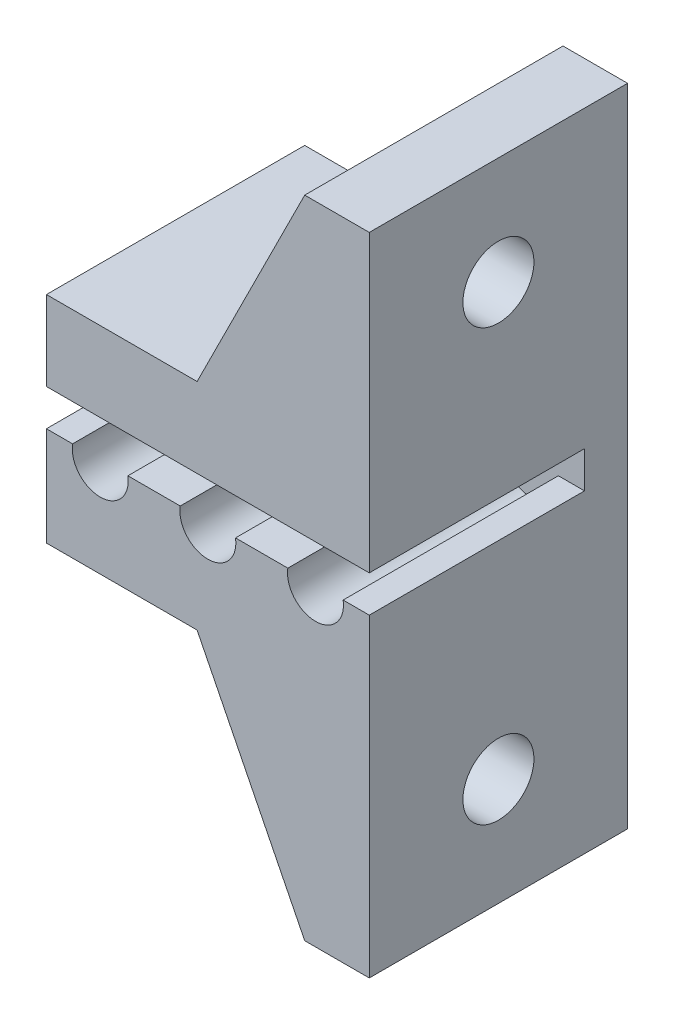
SolidWorks part; units mm, degrees
note: The reader was unsure of these and kept them because the rebuilt part matched: shared geometry of "Sketch2<4>".
ref_plane "Front Plane" through (0, 0, 0) normal (0, 0, 1) x (1, 0, 0)
ref_plane "Top Plane" through (0, 0, 0) normal (0, 1, 0) x (1, 0, 0)
ref_plane "Right Plane" through (0, 0, 0) normal (1, 0, 0) x (0, 0, -1)
sketch "Model" plane through (0, 0, 0) normal (0, 0, 1) x (1, 0, 0)
  line L11 (258.5262, 236.0812) -> (148.5257, 236.0812)
  line L13 (256.5897, 234.1812) -> (255.4627, 234.1812)
  line L14 (251.5897, 234.1812) -> (250.4627, 234.1812)
  line L15 (246.5897, 234.1812) -> (245.4627, 234.1812)
  line L16 (241.5897, 234.1812) -> (240.4626, 234.1812)
  line L17 (236.5896, 234.1812) -> (235.4626, 234.1812)
  line L18 (231.5896, 234.1812) -> (230.4626, 234.1812)
  line L19 (226.5896, 234.1812) -> (225.4626, 234.1812)
  line L20 (221.5896, 234.1812) -> (220.4625, 234.1812)
  line L21 (216.5895, 234.1812) -> (215.4625, 234.1812)
  line L22 (211.5895, 234.1812) -> (210.4625, 234.1812)
  line L23 (206.5895, 234.1812) -> (205.4625, 234.1812)
  line L24 (201.5895, 234.1812) -> (200.4624, 234.1812)
  line L25 (196.5894, 234.1812) -> (195.4624, 234.1812)
  line L26 (191.5894, 234.1812) -> (190.4624, 234.1812)
  line L27 (186.5894, 234.1812) -> (185.4624, 234.1812)
  line L28 (181.5894, 234.1812) -> (180.4623, 234.1812)
  line L29 (176.5893, 234.1812) -> (175.4623, 234.1812)
  line L30 (171.5893, 234.1812) -> (170.4623, 234.1812)
  line L31 (166.5893, 234.1812) -> (165.4623, 234.1812)
  line L32 (161.5892, 234.1812) -> (160.4622, 234.1812)
  line L33 (156.5892, 234.1812) -> (155.4622, 234.1812)
  line L34 (151.5892, 234.1812) -> (150.4622, 234.1812)
  line L58 (148.5257, 234.1812) -> (258.5262, 234.1812) construction
  arc A194 (260.2901, 234.1505) -> (259.9786, 233.8062) centre (260.4627, 233.6812) ccw
  arc A195 (258.9429, 232.7402) -> (259.9786, 233.8062) centre (258.5262, 234.1812) ccw
  arc A196 (258.9429, 232.7402) -> (258.1096, 232.7402) centre (258.5262, 232.0185) ccw
  arc A197 (257.0739, 233.8062) -> (258.1096, 232.7402) centre (258.5262, 234.1812) ccw
  arc A198 (257.0739, 233.8062) -> (256.5897, 234.1812) centre (256.5897, 233.6812) ccw
  arc A199 (255.4627, 234.1812) -> (254.9786, 233.8062) centre (255.4627, 233.6812) ccw
  arc A200 (253.9429, 232.7402) -> (254.9786, 233.8062) centre (253.5262, 234.1812) ccw
  arc A201 (253.9429, 232.7402) -> (253.1095, 232.7402) centre (253.5262, 232.0185) ccw
  arc A202 (252.0738, 233.8062) -> (253.1095, 232.7402) centre (253.5262, 234.1812) ccw
  arc A203 (252.0738, 233.8062) -> (251.5897, 234.1812) centre (251.5897, 233.6812) ccw
  arc A204 (250.4627, 234.1812) -> (249.9786, 233.8062) centre (250.4627, 233.6812) ccw
  arc A205 (248.9429, 232.7402) -> (249.9786, 233.8062) centre (248.5262, 234.1812) ccw
  arc A206 (248.9429, 232.7402) -> (248.1095, 232.7402) centre (248.5262, 232.0185) ccw
  arc A207 (247.0738, 233.8062) -> (248.1095, 232.7402) centre (248.5262, 234.1812) ccw
  arc A208 (247.0738, 233.8062) -> (246.5897, 234.1812) centre (246.5897, 233.6812) ccw
  arc A209 (245.4627, 234.1812) -> (244.9785, 233.8062) centre (245.4627, 233.6812) ccw
  arc A210 (243.9428, 232.7402) -> (244.9785, 233.8062) centre (243.5262, 234.1812) ccw
  arc A211 (243.9428, 232.7402) -> (243.1095, 232.7402) centre (243.5262, 232.0185) ccw
  arc A212 (242.0738, 233.8062) -> (243.1095, 232.7402) centre (243.5262, 234.1812) ccw
  arc A213 (242.0738, 233.8062) -> (241.5897, 234.1812) centre (241.5897, 233.6812) ccw
  arc A214 (240.4626, 234.1812) -> (239.9785, 233.8062) centre (240.4626, 233.6812) ccw
  arc A215 (238.9428, 232.7402) -> (239.9785, 233.8062) centre (238.5261, 234.1812) ccw
  arc A216 (238.9428, 232.7402) -> (238.1095, 232.7402) centre (238.5261, 232.0185) ccw
  arc A217 (237.0738, 233.8062) -> (238.1095, 232.7402) centre (238.5261, 234.1812) ccw
  arc A218 (237.0738, 233.8062) -> (236.5896, 234.1812) centre (236.5896, 233.6812) ccw
  arc A219 (235.4626, 234.1812) -> (234.9785, 233.8062) centre (235.4626, 233.6812) ccw
  arc A220 (233.9428, 232.7402) -> (234.9785, 233.8062) centre (233.5261, 234.1812) ccw
  arc A221 (233.9428, 232.7402) -> (233.1094, 232.7402) centre (233.5261, 232.0185) ccw
  arc A222 (232.0737, 233.8062) -> (233.1094, 232.7402) centre (233.5261, 234.1812) ccw
  arc A223 (232.0737, 233.8062) -> (231.5896, 234.1812) centre (231.5896, 233.6812) ccw
  arc A224 (230.4626, 234.1812) -> (229.9785, 233.8062) centre (230.4626, 233.6812) ccw
  arc A225 (228.9428, 232.7402) -> (229.9785, 233.8062) centre (228.5261, 234.1812) ccw
  arc A226 (228.9428, 232.7402) -> (228.1094, 232.7402) centre (228.5261, 232.0185) ccw
  arc A227 (227.0737, 233.8062) -> (228.1094, 232.7402) centre (228.5261, 234.1812) ccw
  arc A228 (227.0737, 233.8062) -> (226.5896, 234.1812) centre (226.5896, 233.6812) ccw
  arc A229 (225.4626, 234.1812) -> (224.9784, 233.8062) centre (225.4626, 233.6812) ccw
  arc A230 (223.9427, 232.7402) -> (224.9784, 233.8062) centre (223.5261, 234.1812) ccw
  arc A231 (223.9427, 232.7402) -> (223.1094, 232.7402) centre (223.5261, 232.0185) ccw
  arc A232 (222.0737, 233.8062) -> (223.1094, 232.7402) centre (223.5261, 234.1812) ccw
  arc A233 (222.0737, 233.8062) -> (221.5896, 234.1812) centre (221.5896, 233.6812) ccw
  arc A234 (220.4625, 234.1812) -> (219.9784, 233.8062) centre (220.4625, 233.6812) ccw
  arc A235 (218.9427, 232.7402) -> (219.9784, 233.8062) centre (218.526, 234.1812) ccw
  arc A236 (218.9427, 232.7402) -> (218.1094, 232.7402) centre (218.526, 232.0185) ccw
  arc A237 (217.0737, 233.8062) -> (218.1094, 232.7402) centre (218.526, 234.1812) ccw
  arc A238 (217.0737, 233.8062) -> (216.5895, 234.1812) centre (216.5895, 233.6812) ccw
  arc A239 (215.4625, 234.1812) -> (214.9784, 233.8062) centre (215.4625, 233.6812) ccw
  arc A240 (213.9427, 232.7402) -> (214.9784, 233.8062) centre (213.526, 234.1812) ccw
  arc A241 (213.9427, 232.7402) -> (213.1093, 232.7402) centre (213.526, 232.0185) ccw
  arc A242 (212.0736, 233.8062) -> (213.1093, 232.7402) centre (213.526, 234.1812) ccw
  arc A243 (212.0736, 233.8062) -> (211.5895, 234.1812) centre (211.5895, 233.6812) ccw
  arc A244 (210.4625, 234.1812) -> (209.9784, 233.8062) centre (210.4625, 233.6812) ccw
  arc A245 (208.9427, 232.7402) -> (209.9784, 233.8062) centre (208.526, 234.1812) ccw
  arc A246 (208.9427, 232.7402) -> (208.1093, 232.7402) centre (208.526, 232.0185) ccw
  arc A247 (207.0736, 233.8062) -> (208.1093, 232.7402) centre (208.526, 234.1812) ccw
  arc A248 (207.0736, 233.8062) -> (206.5895, 234.1812) centre (206.5895, 233.6812) ccw
  arc A249 (205.4625, 234.1812) -> (204.9783, 233.8062) centre (205.4625, 233.6812) ccw
  arc A250 (203.9426, 232.7402) -> (204.9783, 233.8062) centre (203.526, 234.1812) ccw
  arc A251 (203.9426, 232.7402) -> (203.1093, 232.7402) centre (203.526, 232.0185) ccw
  arc A252 (202.0736, 233.8062) -> (203.1093, 232.7402) centre (203.526, 234.1812) ccw
  arc A253 (202.0736, 233.8062) -> (201.5895, 234.1812) centre (201.5895, 233.6812) ccw
  arc A254 (200.4624, 234.1812) -> (199.9783, 233.8062) centre (200.4624, 233.6812) ccw
  arc A255 (198.9426, 232.7402) -> (199.9783, 233.8062) centre (198.5259, 234.1812) ccw
  arc A256 (198.9426, 232.7402) -> (198.1093, 232.7402) centre (198.5259, 232.0185) ccw
  arc A257 (197.0736, 233.8062) -> (198.1093, 232.7402) centre (198.5259, 234.1812) ccw
  arc A258 (197.0736, 233.8062) -> (196.5894, 234.1812) centre (196.5894, 233.6812) ccw
  arc A259 (195.4624, 234.1812) -> (194.9783, 233.8062) centre (195.4624, 233.6812) ccw
  arc A260 (193.9426, 232.7402) -> (194.9783, 233.8062) centre (193.5259, 234.1812) ccw
  arc A261 (193.9426, 232.7402) -> (193.1092, 232.7402) centre (193.5259, 232.0185) ccw
  arc A262 (192.0735, 233.8062) -> (193.1092, 232.7402) centre (193.5259, 234.1812) ccw
  arc A263 (192.0735, 233.8062) -> (191.5894, 234.1812) centre (191.5894, 233.6812) ccw
  arc A264 (190.4624, 234.1812) -> (189.9783, 233.8062) centre (190.4624, 233.6812) ccw
  arc A265 (188.9425, 232.7402) -> (189.9783, 233.8062) centre (188.5259, 234.1812) ccw
  arc A266 (188.9425, 232.7402) -> (188.1092, 232.7402) centre (188.5259, 232.0185) ccw
  arc A267 (187.0735, 233.8062) -> (188.1092, 232.7402) centre (188.5259, 234.1812) ccw
  arc A268 (187.0735, 233.8062) -> (186.5894, 234.1812) centre (186.5894, 233.6812) ccw
  arc A269 (185.4624, 234.1812) -> (184.9782, 233.8062) centre (185.4624, 233.6812) ccw
  arc A270 (183.9425, 232.7402) -> (184.9782, 233.8062) centre (183.5259, 234.1812) ccw
  arc A271 (183.9425, 232.7402) -> (183.1092, 232.7402) centre (183.5259, 232.0185) ccw
  arc A272 (182.0735, 233.8062) -> (183.1092, 232.7402) centre (183.5259, 234.1812) ccw
  arc A273 (182.0735, 233.8062) -> (181.5894, 234.1812) centre (181.5894, 233.6812) ccw
  arc A274 (180.4623, 234.1812) -> (179.9782, 233.8062) centre (180.4623, 233.6812) ccw
  arc A275 (178.9425, 232.7402) -> (179.9782, 233.8062) centre (178.5258, 234.1812) ccw
  arc A276 (178.9425, 232.7402) -> (178.1092, 232.7402) centre (178.5258, 232.0185) ccw
  arc A277 (177.0735, 233.8062) -> (178.1092, 232.7402) centre (178.5258, 234.1812) ccw
  arc A278 (177.0735, 233.8062) -> (176.5893, 234.1812) centre (176.5893, 233.6812) ccw
  arc A279 (175.4623, 234.1812) -> (174.9782, 233.8062) centre (175.4623, 233.6812) ccw
  arc A280 (173.9425, 232.7402) -> (174.9782, 233.8062) centre (173.5258, 234.1812) ccw
  arc A281 (173.9425, 232.7402) -> (173.1091, 232.7402) centre (173.5258, 232.0185) ccw
  arc A282 (172.0734, 233.8062) -> (173.1091, 232.7402) centre (173.5258, 234.1812) ccw
  arc A283 (172.0734, 233.8062) -> (171.5893, 234.1812) centre (171.5893, 233.6812) ccw
  arc A284 (170.4623, 234.1812) -> (169.9782, 233.8062) centre (170.4623, 233.6812) ccw
  arc A285 (168.9424, 232.7402) -> (169.9782, 233.8062) centre (168.5258, 234.1812) ccw
  arc A286 (168.9424, 232.7402) -> (168.1091, 232.7402) centre (168.5258, 232.0185) ccw
  arc A287 (167.0734, 233.8062) -> (168.1091, 232.7402) centre (168.5258, 234.1812) ccw
  arc A288 (167.0734, 233.8062) -> (166.5893, 234.1812) centre (166.5893, 233.6812) ccw
  arc A289 (165.4623, 234.1812) -> (164.9781, 233.8062) centre (165.4623, 233.6812) ccw
  arc A290 (163.9424, 232.7402) -> (164.9781, 233.8062) centre (163.5258, 234.1812) ccw
  arc A291 (163.9424, 232.7402) -> (163.1091, 232.7402) centre (163.5258, 232.0185) ccw
  arc A292 (162.0734, 233.8062) -> (163.1091, 232.7402) centre (163.5258, 234.1812) ccw
  arc A293 (162.0734, 233.8062) -> (161.5892, 234.1812) centre (161.5892, 233.6812) ccw
  arc A294 (160.4622, 234.1812) -> (159.9781, 233.8062) centre (160.4622, 233.6812) ccw
  arc A295 (158.9424, 232.7402) -> (159.9781, 233.8062) centre (158.5257, 234.1812) ccw
  arc A296 (158.9424, 232.7402) -> (158.1091, 232.7402) centre (158.5257, 232.0185) ccw
  arc A297 (157.0733, 233.8062) -> (158.1091, 232.7402) centre (158.5257, 234.1812) ccw
  arc A298 (157.0733, 233.8062) -> (156.5892, 234.1812) centre (156.5892, 233.6812) ccw
  arc A299 (155.4622, 234.1812) -> (154.9781, 233.8062) centre (155.4622, 233.6812) ccw
  arc A300 (153.9424, 232.7402) -> (154.9781, 233.8062) centre (153.5257, 234.1812) ccw
  arc A301 (153.9424, 232.7402) -> (153.109, 232.7402) centre (153.5257, 232.0185) ccw
  arc A302 (152.0733, 233.8062) -> (153.109, 232.7402) centre (153.5257, 234.1812) ccw
  arc A303 (152.0733, 233.8062) -> (151.5892, 234.1812) centre (151.5892, 233.6812) ccw
  arc A304 (150.4622, 234.1812) -> (149.978, 233.8062) centre (150.4622, 233.6812) ccw
  arc A305 (148.9423, 232.7402) -> (149.978, 233.8062) centre (148.5257, 234.1812) ccw
  arc A306 (148.9423, 232.7402) -> (148.109, 232.7402) centre (148.5257, 232.0185) ccw
  arc A307 (147.0733, 233.8062) -> (148.109, 232.7402) centre (148.5257, 234.1812) ccw
  arc A308 (147.0733, 233.8062) -> (146.7618, 234.1505) centre (146.5892, 233.6812) ccw
  point P0 (0, 0)
sketch "Sketch2" plane through (0, 0, 0) normal (0, 0, 1) x (1, 0, 0)
  line L0 (0, 5) -> (0, -5)
  line L1 (0, -5) -> (12, -5)
  line L2 (12, -5) -> (12, -15)
  line L3 (12, -15) -> (15, -15)
  line L4 (15, -15) -> (15, 15)
  line L5 (15, 15) -> (12, 15)
  line L6 (12, 15) -> (12, 5)
  line L7 (12, 5) -> (0, 5)
  line L8 (0, 1.3) -> (15, 1.3)
  line L9 (0, -0.6) -> (15, -0.6) construction
  line L10 (2.5, -0.6) -> (7.5, -0.6) construction
  line L11 (7.5, -0.6) -> (12.5, -0.6) construction
  line L12 (0, -0.4) -> (1.2155, -0.4)
  line L13 (0, -0.6) -> (1, -0.6)
  line L14 (4, -0.6) -> (6, -0.6)
  line L15 (9, -0.6) -> (11, -0.6)
  line L16 (14, -0.6) -> (15, -0.6)
  line L17 (3.7845, -0.4) -> (6.2155, -0.4)
  line L18 (8.7845, -0.4) -> (11.2155, -0.4)
  line L19 (13.7845, -0.4) -> (15, -0.4)
  arc A0 (1, -0.6) -> (4, -0.6) centre (2.5, -0.6) ccw
  arc A1 (6, -0.6) -> (9, -0.6) centre (7.5, -0.6) ccw
  arc A2 (11, -0.6) -> (14, -0.6) centre (12.5, -0.6) ccw
  arc A3 (1.2155, -0.4) -> (3.7845, -0.4) centre (2.5, -0.6) ccw
  arc A4 (6.2155, -0.4) -> (8.7845, -0.4) centre (7.5, -0.6) ccw
  arc A5 (11.2155, -0.4) -> (13.7845, -0.4) centre (12.5, -0.6) ccw
  point P12 (0, 0)
  point P20 (15, 0)
  point P24 (7.5, -0.6)
  dimension "D6" = 1.5
  dimension "D1" = 15
  dimension "D2" = 3
  dimension "D4" = 10
  dimension "D5" = 10
  dimension "D7" = 5
  dimension "D8" = 1.9
  dimension "D9" = 1.3
  dimension "D10" = 0.2
extrude "Boss-Extrude1" add sketch "Sketch2" along normal blind 10 contours A2 L15 A1 L14 A0 L13 L0 L1 L2 L3 L4 L16 | L0 L8 L4 L5 L6 L7 | A5 L18 A4 L17 A3 L12 L0 L13 A0 L14 A1 L15 A2 L16 L4 L19
extrude "Boss-Extrude2" add sketch "Sketch2<4>" against normal blind 2 contours L0 L8 L4 L5 L6 L7 | L15 A2 L16 L4 L8 L0 L13 A0 L14 A1 | L18 A5 L19 L4 L16 A2 L15 A1 L14 A0 L13 L0 L12 A3 L17 A4 | A5 L18 A4 L17 A3 L12 L0 L1 L2 L3 L4 L19
sketch "Sketch2<4>" plane through (0, 0, 0) normal (0, 0, 1) x (1, 0, 0) same geometry as "Sketch2"
sketch "Sketch5" plane through (12, 0, 0) normal (-1, 0, 0) x (0, 0, 1)
  line L0 (-2, 5) -> (10, 15) construction
  line L1 (-2, 15) -> (10, 5) construction
  circle A0 centre (4, 10) radius 1.65
  dimension "D1" = 3.3
extrude "Cut-Extrude1" cut sketch "Sketch5" against normal up to next
sketch "Sketch4" plane through (0, 0, 10) normal (0, 0, 1) x (1, 0, 0)
  line L0 (7, 5) -> (12, 15)
  line L1 (12, 5) -> (0, 5) construction
  line L2 (12, 15) -> (12, 5) construction
  line L3 (15, 15) -> (12, 15) construction
  point P6 (12, 15)
  dimension "D1" = 5
rib "Rib1" sketch "Sketch4" sketch "Sketch4" thickness 1.5 extrusion direction parallel to sketch draft on no parameters "D1"=1.5
ref_plane "Plane1" through (0, 0, 4) normal (0, 0, 1) x (1, 0, 0)
ref_plane "Plane2" through (0, 0, 0) normal (0, 1, 0) x (1, 0, 0)
mirror "Mirror1" about plane through (0, 0, 4) normal (0, 0, 1) of "Rib1"
mirror "Mirror2" about plane through (0, 0, 0) normal (0, 1, 0) of "Cut-Extrude1", "Mirror1", "Rib1"
